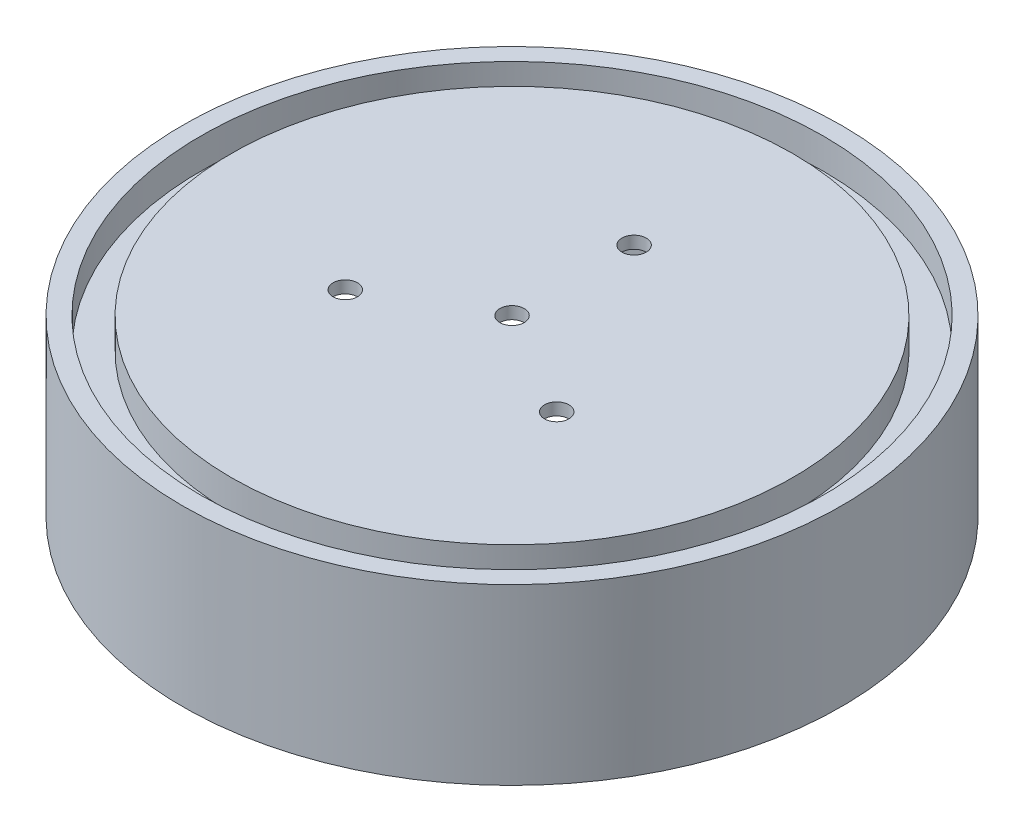
SolidWorks part; units mm, degrees
ref_plane "前视基准面" through (0, 0, 0) normal (0, 0, 1) x (1, 0, 0)
ref_plane "上视基准面" through (0, 0, 0) normal (0, 1, 0) x (1, 0, 0)
ref_plane "右视基准面" through (0, 0, 0) normal (1, 0, 0) x (0, 0, -1)
sketch "草图1" plane through (0, 0, 0) normal (0, 1, 0) x (1, 0, 0)
  circle A0 centre (0, 0) radius 54
extrude "凸台-拉伸1" add sketch "草图1" along normal blind 25
sketch "草图3" plane through (0, 25, 0) normal (0, 1, 0) x (1, 0, 0)
  circle A0 centre (0, 0) radius 51
  circle A1 centre (0, 0) radius 46
  dimension "D1" = 92
extrude "切除-拉伸1" cut sketch "草图3" against normal blind 5
sketch "草图4" plane through (0, 0, 0) normal (0, -1, 0) x (1, 0, 0)
  circle A0 centre (0, 0) radius 51
  dimension "D1" = 102
extrude "切除-拉伸2" cut sketch "草图4" against normal blind 18
sketch "草图5" plane through (0, 18, 0) normal (0, -1, 0) x (1, 0, 0)
  circle A1 centre (0, 0) radius 38
extrude "切除-拉伸3" cut sketch "草图5" against normal blind 5
sketch "草图7" plane through (0, 0, 0) normal (0, 0, 1) x (1, 0, 0)
  line L1 (-6, 14) -> (6, 14)
  line L2 (-6, 14) -> (-6, 6)
  line L3 (-6, 6) -> (6, 6)
  line L4 (6, 14) -> (6, 6)
  line L5 (-6, 14) -> (6, 6) construction
  line L6 (-6, 6) -> (6, 14) construction
  point P0 (0, 10)
extrude "切除-拉伸4" cut sketch "草图7" against normal blind 66
sketch "草图8" plane through (0, 18, 0) normal (0, -1, 0) x (1, 0, 0)
  line L1 (6, -41.5) -> (-6, -41.5)
  line L2 (6, -41.5) -> (6, -38.5)
  line L3 (6, -38.5) -> (-6, -38.5)
  line L4 (-6, -41.5) -> (-6, -38.5)
  line L5 (6, -41.5) -> (-6, -38.5) construction
  line L6 (6, -38.5) -> (-6, -41.5) construction
  circle A0 centre (-35.0001, -32) radius 1
  circle A1 centre (35.0001, -32) radius 1
  circle A2 centre (-35.0001, -32) radius 3
  circle A3 centre (35.0001, -32) radius 3
  point P6 (0, -40)
extrude "凸台-拉伸2" add sketch "草图8" along normal blind 5
sketch "草图9" plane through (0, 18, 0) normal (0, -1, 0) x (1, 0, 0)
  line L0 (15.3357, -41.9458) -> (22.133, -38.7762)
  line L1 (22.133, -38.7762) -> (22.9783, -40.5888)
  line L2 (22.9783, -40.5888) -> (16.1809, -43.7584)
  line L3 (16.1809, -43.7584) -> (15.3357, -41.9458)
extrude "凸台-拉伸3" add sketch "草图9" along normal blind 5
sketch "草图10" plane through (18.8052, 0, -40.3279) normal (-0.4226, 0, 0.9063) x (0.9063, 0, 0.4226)
  circle A0 centre (-0.1, 7.3) radius 2
extrude "切除-拉伸5" cut sketch "草图10" against normal blind 29
fillet "圆角1" radius 2 4 edges at (-6, 6, -52.1557) (-6, 14, -52.1557) (6, 14, -52.1557) (6, 6, -52.1557)
sketch "草图12" plane through (0, 0, 0) normal (0, -1, 0) x (1, 0, 0)
  circle A0 centre (0, 0) radius 51
  circle A1 centre (0, 0) radius 54
extrude "凸台-拉伸4" add sketch "草图12" along normal blind 3.5
sketch "草图13" plane through (0, 18, 0) normal (0, -1, 0) x (1, 0, 0)
  line L0 (0, 0.0985) -> (0, 41.5985) construction
  line L1 (0, 0.0985) -> (-35.9401, -20.6515) construction
  line L2 (0, 0.0985) -> (35.9401, -20.6515) construction
  circle A0 centre (0, 41.5985) radius 1
  circle A3 centre (0, 41.5985) radius 3.5
  circle A5 centre (35.9401, -20.6515) radius 1
  circle A6 centre (35.9401, -20.6515) radius 3.5
  circle A7 centre (-35.9401, -20.6515) radius 1
  circle A8 centre (-35.9401, -20.6515) radius 3.5
extrude "凸台-拉伸5" add sketch "草图13" along normal blind 19
sketch "草图14" plane through (0, 18, 0) normal (0, -1, 0) x (1, 0, 0)
  line L0 (0, 0) -> (-35.9401, -20.6515) construction
  line L1 (1.8018, 44.1005) -> (-1.8018, 44.1005)
  line L2 (1.8018, 44.1005) -> (1.8018, 52.5069)
  line L3 (1.8018, 52.5069) -> (-1.8018, 52.5069)
  line L4 (-1.8018, 44.1005) -> (-1.8018, 52.5069)
  line L5 (1.8018, 44.1005) -> (-1.8018, 52.5069) construction
  line L6 (1.8018, 52.5069) -> (-1.8018, 44.1005) construction
  line L12 (-35.9401, -20.6515) -> (-41.0904, -23.6109) construction
  line L17 (0, 0) -> (35.9401, -20.6515) construction
  line L18 (35.9401, -20.6515) -> (41.0904, -23.6109) construction
  line L19 (-36.9966, -23.3911) -> (-38.839, -20.1847)
  line L20 (-38.839, -20.1847) -> (-45.7554, -24.1589)
  line L21 (-45.7554, -24.1589) -> (-43.913, -27.3653)
  line L22 (-43.913, -27.3653) -> (-36.9966, -23.3911)
  line L23 (0, -15.675) -> (0, 15.675) construction
  line L24 (43.913, -27.3653) -> (36.9966, -23.3911)
  line L25 (45.7554, -24.1589) -> (43.913, -27.3653)
  line L26 (38.839, -20.1847) -> (45.7554, -24.1589)
  line L27 (36.9966, -23.3911) -> (38.839, -20.1847)
  point P0 (0, 48.3037)
  point P13 (-37.9178, -21.7879)
  point P21 (37.9178, -21.7879)
extrude "凸台-拉伸6" add sketch "草图14" along normal blind 15
fillet "圆角2" radius 1.5 1 edges at (20.95, 6.8415, -49.7704) conic radius 10
sketch "草图15" plane through (0, 25, 0) normal (0, 1, 0) x (1, 0, 0)
  line L0 (0, 0) -> (0, 20) construction
  line L1 (0, 0) -> (-17.3205, -10) construction
  line L2 (0, 0) -> (17.3205, -10) construction
  circle A0 centre (0, 0) radius 2
  circle A1 centre (0, 20) radius 2
  circle A2 centre (-17.3205, -10) radius 2
  circle A3 centre (17.3205, -10) radius 2
extrude "切除-拉伸6" cut sketch "草图15" against normal blind 10
